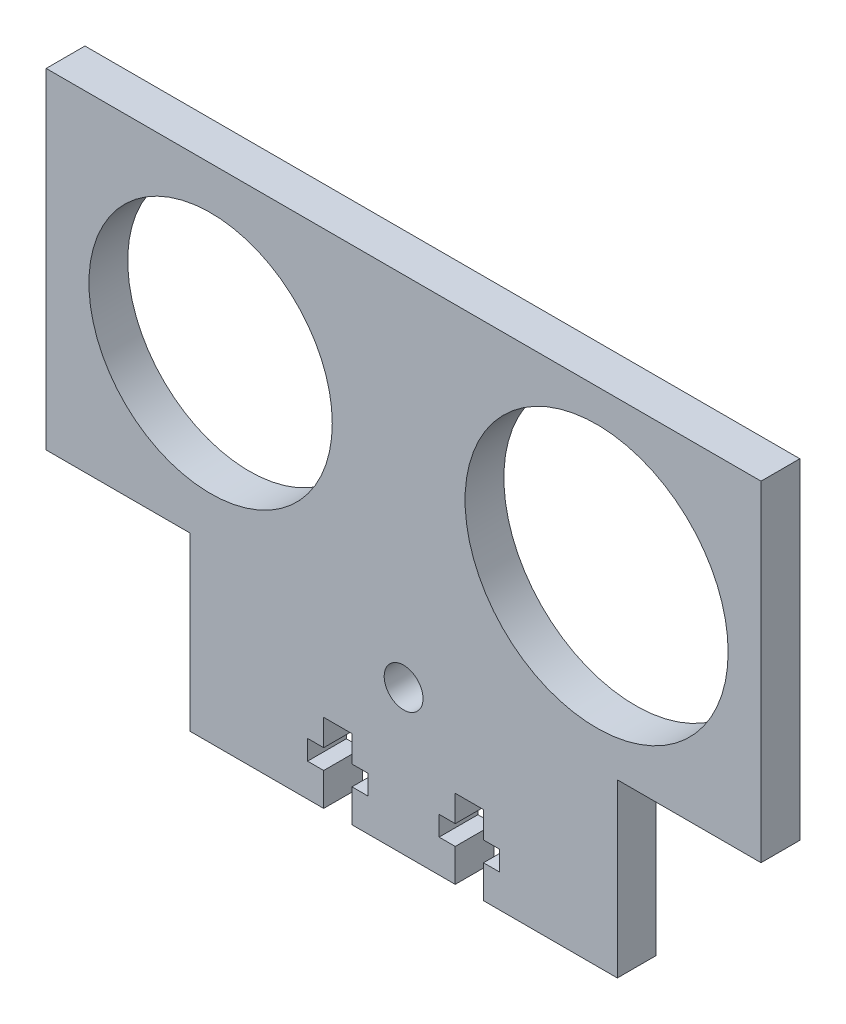
SolidWorks part; units mm, degrees
ref_plane "Front Plane" through (0, 0, 0) normal (0, 0, 1) x (1, 0, 0)
ref_plane "Top Plane" through (0, 0, 0) normal (0, 1, 0) x (1, 0, 0)
ref_plane "Right Plane" through (0, 0, 0) normal (1, 0, 0) x (0, 0, -1)
sketch "Sketch1" plane through (0, 0, 0) normal (0, 0, 1) x (1, 0, 0)
  line L0 (0, 0) -> (-29.3449, 29.3449) construction
  line L1 (0, 0) -> (0, 54.3449) construction
  line L2 (-32.5, 4.1) -> (-32.5, -22)
  line L3 (-32.5, -22) -> (32.5, -22)
  line L4 (32.5, -22) -> (32.5, 4.1)
  line L5 (0, 0) -> (0, -22) construction
  line L6 (0, 0) -> (29.3449, 29.3449) construction
  line L10 (-32.5, 4.1) -> (-54.3449, 4.1)
  line L11 (-54.3449, 4.1) -> (-54.3449, 54.3449)
  line L12 (-54.3449, 54.3449) -> (54.3449, 54.3449)
  line L13 (54.3449, 54.3449) -> (54.3449, 4.1)
  line L14 (54.3449, 4.1) -> (32.5, 4.1)
  circle A0 centre (0, 0) radius 2.95
  circle A1 centre (29.3449, 29.3449) radius 20
  circle A2 centre (-29.3449, 29.3449) radius 18.5
  dimension "D1" = 5.9
  dimension "D9" = 37
  dimension "D11" = 40
  dimension "D2" = 41.5
  dimension "D4" = 45
  dimension "D5" = 22
  dimension "D6" = 65
  dimension "D3" = 25
  dimension "D7" = 25
  dimension "D8" = 26.1
  dimension "D10" = 45
extrude "Boss-Extrude1" add sketch "Sketch1" along normal blind 5.9
sketch "Sketch3" plane through (0, 0, 5.9) normal (0, 0, 1) x (1, 0, 0)
  line L0 (-32.5, -22) -> (32.5, -22) construction
  line L1 (-12.15, -22) -> (-7.85, -22)
  line L2 (-12.15, -22) -> (-12.15, -17)
  line L3 (-12.15, -10) -> (-7.85, -10)
  line L4 (-7.85, -22) -> (-7.85, -17)
  line L5 (0, 0) -> (0, -22) construction
  line L6 (-7.85, -14) -> (-5.4, -14)
  line L7 (-14.6, -14) -> (-12.15, -14)
  line L8 (-14.6, -14) -> (-14.6, -17)
  line L9 (-14.6, -17) -> (-12.15, -17)
  line L10 (-5.4, -14) -> (-5.4, -17)
  line L11 (-12.15, -14) -> (-12.15, -10)
  line L12 (-7.85, -17) -> (-5.4, -17)
  line L13 (-7.85, -14) -> (-7.85, -10)
  line L14 (7.85, -14) -> (7.85, -10)
  line L15 (7.85, -17) -> (5.4, -17)
  line L16 (12.15, -14) -> (12.15, -10)
  line L17 (5.4, -14) -> (5.4, -17)
  line L18 (14.6, -17) -> (12.15, -17)
  line L19 (14.6, -14) -> (14.6, -17)
  line L20 (14.6, -14) -> (12.15, -14)
  line L21 (7.85, -14) -> (5.4, -14)
  line L22 (7.85, -22) -> (7.85, -17)
  line L23 (12.15, -10) -> (7.85, -10)
  line L24 (12.15, -22) -> (12.15, -17)
  line L25 (12.15, -22) -> (7.85, -22)
  point P6 (-10, -10)
  point P18 (-13.375, -17)
  dimension "D1" = 4.3
  dimension "D2" = 10
  dimension "D3" = 12
  dimension "D4" = 9.2
  dimension "D5" = 3
  dimension "D6" = 5
extrude "Cut-Extrude2" cut sketch "Sketch3" against normal through all
equation "\"smallPulleyTeeth\"= 15"
equation "\"largePulleyTeeth\"= 30"
equation "\"eighthThick\"= 2.9mm"
equation "\"sixteenthThick\" = 1.7mm"
equation "\"quarterThick\"=5.9mm"
equation "\"OD\" = 145mm"
equation "\"puckAngle\" = 60.5deg"
equation "\"puckDiam\" = 76.5mm"
equation "\"axlePress\" = 5.9mm"
equation "\"D1@Sketch1\"=\"axlePress\""
equation "\"D1@Boss-Extrude1\"=\"quarterThick\""
equation "\"press\" = 0.2mm"
equation "\"wheelClear\" = 0.3mm"
equation "\"10-32clear\" = 4.5mm"
equation "\"D1@Sketch3\"=\"10-32clear\"-\"press\""
equation "\"6-32clear\" = 3.3mm"
equation "\"8-32clear\" = 4.0mm"
equation "\"wheelHeight\" = 22mm"
equation "\"D5@Sketch1\"=\"wheelHeight\""
equation "\"D8@Sketch1\"=\"eighthThick\"*9"
equation "\"4-40clear\" = 2.55mm"
equation "\"wheelWell\" = 65mm"
equation "\"D6@Sketch1\"=\"wheelWell\""
